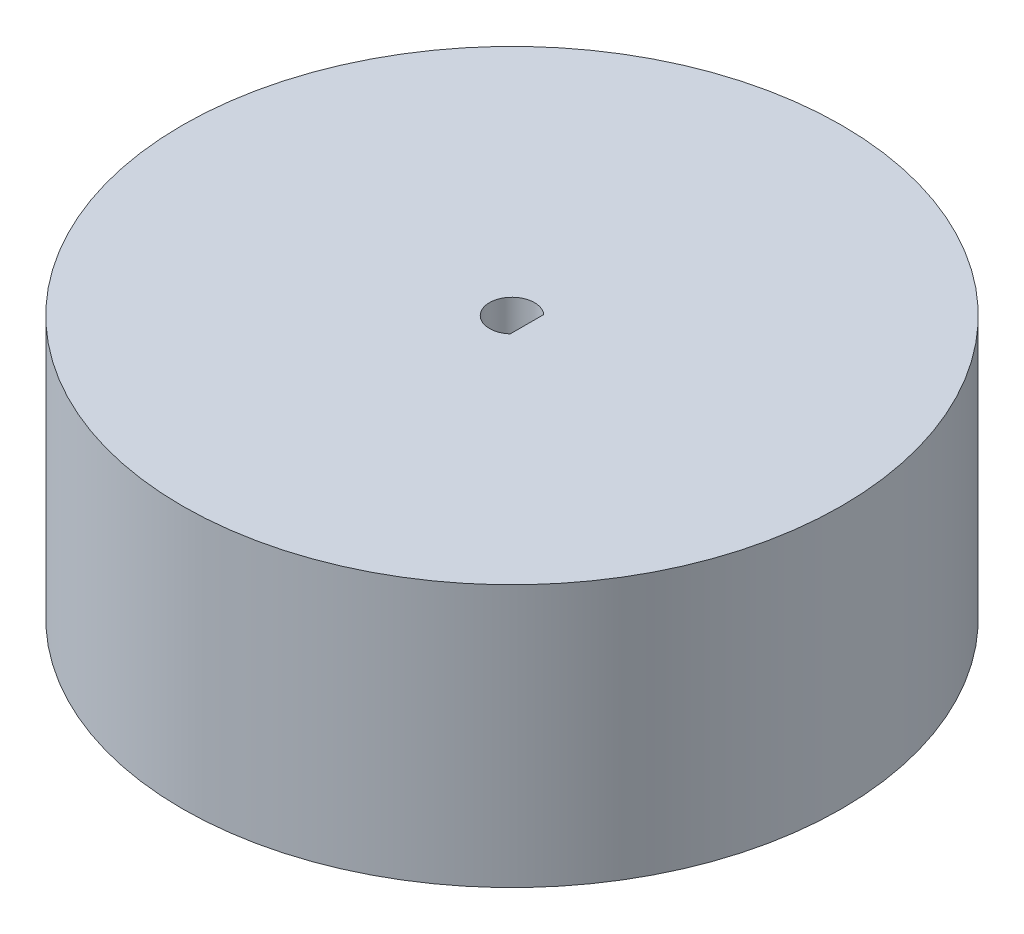
SolidWorks part; units mm, degrees
ref_plane "Front Plane" through (0, 0, 0) normal (0, 0, 1) x (1, 0, 0)
ref_plane "Top Plane" through (0, 0, 0) normal (0, 1, 0) x (1, 0, 0)
ref_plane "Right Plane" through (0, 0, 0) normal (1, 0, 0) x (0, 0, -1)
sketch "Sketch1" plane through (0, 0, 0) normal (0, 1, 0) x (1, 0, 0)
  circle A0 centre (0, 0) radius 22
  dimension "D1" = 44
extrude "Boss-Extrude1" add sketch "Sketch1" along normal blind 17.5
sketch "Sketch2" plane through (0, 17.5, 0) normal (0, 1, 0) x (1, 0, 0)
  line L0 (1, 1.118) -> (1, -1.118)
  arc A0 (1, 1.118) -> (1, -1.118) centre (0, 0) ccw
  dimension "D1" = 3
  dimension "D2" = 1
extrude "Cut-Extrude1" cut sketch "Sketch2" against normal up to next
sketch "Sketch3" plane through (0, 0, 0) normal (0, -1, 0) x (1, 0, 0)
  circle A0 centre (0, 0) radius 12
  circle A1 centre (0, 0) radius 22 construction
  dimension "D1" = 10
extrude "Cut-Extrude2" cut sketch "Sketch3" against normal blind 13
